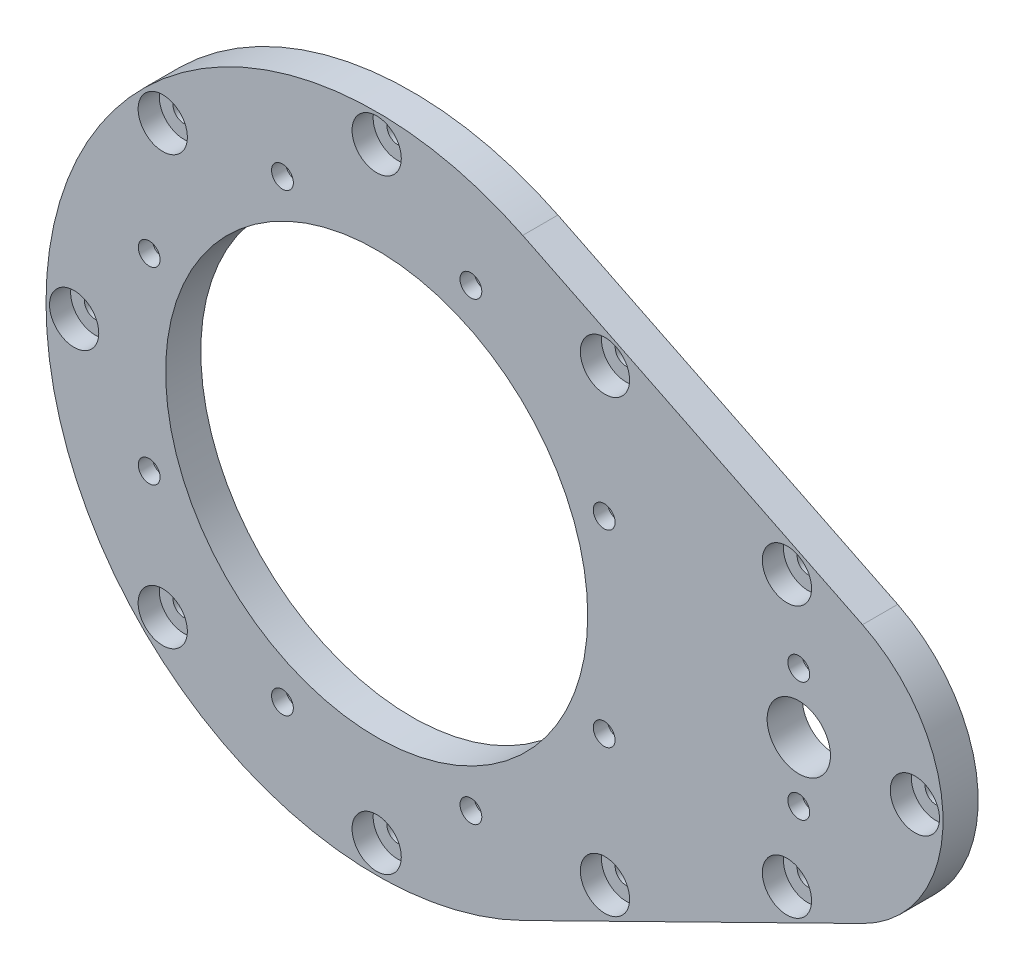
SolidWorks part; units mm, degrees
ref_plane "Front Plane" through (0, 0, 0) normal (0, 0, 1) x (1, 0, 0)
ref_plane "Top Plane" through (0, 0, 0) normal (0, 1, 0) x (1, 0, 0)
ref_plane "Right Plane" through (0, 0, 0) normal (1, 0, 0) x (0, 0, -1)
sketch "Sketch1" plane through (0, 0, 0) normal (0, 0, 1) x (1, 0, 0)
  line L0 (60, -8.5) -> (60, 8.5) construction
  line L1 (0, 0) -> (60, 0) construction
  line L6 (69.0542, 18.3922) -> (20.7583, 42.1674)
  line L7 (69.0542, -18.3922) -> (20.7583, -42.1674)
  line L8 (0, 0) -> (0, 43) construction
  line L9 (0, 0) -> (32.3358, 13.3939) construction
  line L10 (20.7583, 42.1674) -> (34.216, 35.5424) construction
  line L11 (34.216, 35.5424) -> (32.4494, 31.9537) construction
  line L12 (69.0542, 18.3922) -> (60.0824, 22.8088) construction
  line L13 (60.0824, 22.8088) -> (58.3157, 19.2201) construction
  line L14 (20.7583, -42.1674) -> (34.216, -35.5424) construction
  line L15 (34.216, -35.5424) -> (32.4494, -31.9537) construction
  line L16 (69.0542, -18.3922) -> (60.0824, -22.8088) construction
  line L17 (60.0824, -22.8088) -> (58.3157, -19.2201) construction
  line L18 (60, 0) -> (76.5, 0) construction
  circle A1 centre (0, 0) radius 47 construction
  circle A11 centre (60, 0) radius 20.5 construction
  circle A14 centre (60, 8.5) radius 1.55
  circle A15 centre (60, -8.5) radius 1.55
  circle A16 centre (60, 0) radius 4.5
  circle A17 centre (0, 0) radius 30
  circle A18 centre (0, 0) radius 35 construction
  arc A27 (69.0542, 18.3922) -> (69.0542, -18.3922) centre (60, 0) cw
  arc A28 (20.7583, 42.1674) -> (20.7583, -42.1674) centre (0, 0) ccw
  circle A29 centre (0, 43) radius 1.55
  circle A30 centre (-30.4056, 30.4056) radius 1.55
  circle A31 centre (-43, 0) radius 1.55
  circle A32 centre (-30.4056, -30.4056) radius 1.55
  circle A33 centre (0, -43) radius 1.55
  circle A34 centre (32.3358, 13.3939) radius 1.55
  circle A35 centre (32.3358, -13.3939) radius 1.55
  circle A36 centre (13.3939, -32.3358) radius 1.55
  circle A37 centre (-13.3939, -32.3358) radius 1.55
  circle A38 centre (-32.3358, -13.3939) radius 1.55
  circle A39 centre (-32.3358, 13.3939) radius 1.55
  circle A40 centre (-13.3939, 32.3358) radius 1.55
  circle A41 centre (13.3939, 32.3358) radius 1.55
  circle A42 centre (32.4494, 31.9537) radius 1.55
  circle A43 centre (58.3157, 19.2201) radius 1.55
  circle A44 centre (32.4494, -31.9537) radius 1.55
  circle A45 centre (58.3157, -19.2201) radius 1.55
  circle A46 centre (76.5, 0) radius 1.55
  point P7 (60, 0)
  point P22 (0, 0)
  point P30 (0, 0)
  point P36 (0, 0)
  point P48 (0, 0)
extrude "Boss-Extrude2" add sketch "Sketch1" along normal blind 5
sketch "Sketch2" plane through (0, 0, 0) normal (0, 0, -1) x (-1, 0, 0)
  circle A0 centre (-60, 8.5) radius 3.5
  circle A1 centre (-60, -8.5) radius 3.5
  circle A10 centre (-13.3939, 32.3358) radius 3.5
  circle A11 centre (13.3939, 32.3358) radius 3.5
  circle A12 centre (32.3358, 13.3939) radius 3.5
  circle A13 centre (32.3358, -13.3939) radius 3.5
  circle A14 centre (13.3939, -32.3358) radius 3.5
  circle A15 centre (-13.3939, -32.3358) radius 3.5
  circle A16 centre (-32.3358, -13.3939) radius 3.5
  circle A17 centre (-32.3358, 13.3939) radius 3.5
  point P25 (0, 0)
extrude "Cut-Extrude1" cut sketch "Sketch2" against normal blind 3
sketch "Sketch3" plane through (0, 0, 5) normal (0, 0, 1) x (1, 0, 0)
  circle A0 centre (0, 43) radius 3.5
  circle A1 centre (-30.4056, 30.4056) radius 3.5
  circle A2 centre (-43, 0) radius 3.5
  circle A3 centre (-30.4056, -30.4056) radius 3.5
  circle A4 centre (0, -43) radius 3.5
  circle A5 centre (32.4494, 31.9537) radius 3.5
  circle A6 centre (58.3157, 19.2201) radius 3.5
  circle A7 centre (32.4494, -31.9537) radius 3.5
  circle A8 centre (58.3157, -19.2201) radius 3.5
  circle A9 centre (76.5, 0) radius 3.5
  point P13 (0, 0)
extrude "Cut-Extrude2" cut sketch "Sketch3" against normal blind 3
